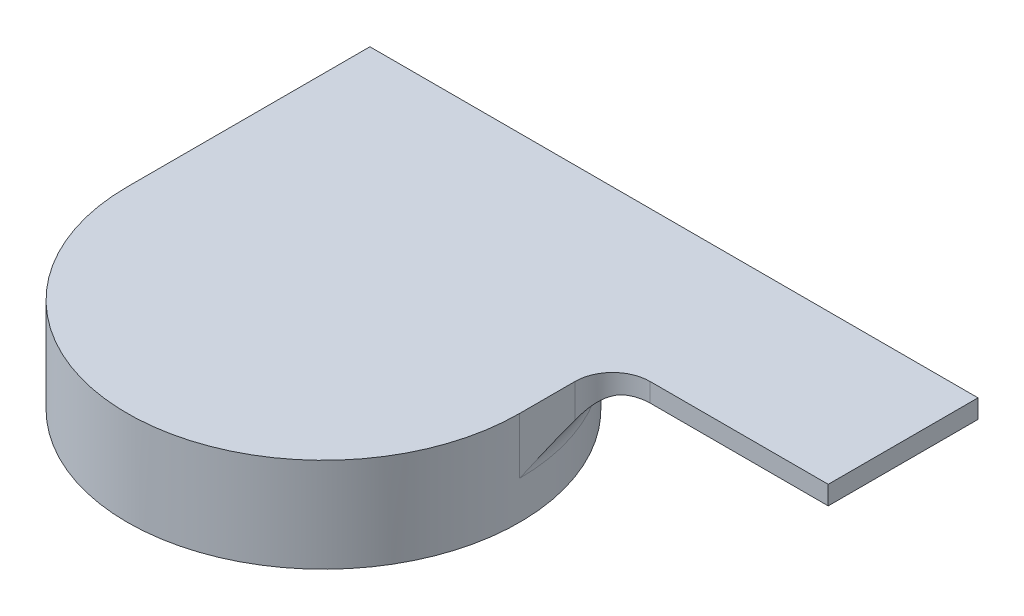
SolidWorks part; units mm, degrees
ref_plane "Front Plane" through (0, 0, 0) normal (0, 0, 1) x (1, 0, 0)
ref_plane "Top Plane" through (0, 0, 0) normal (0, 1, 0) x (1, 0, 0)
ref_plane "Right Plane" through (0, 0, 0) normal (1, 0, 0) x (0, 0, -1)
sketch "Sketch1" plane through (0, 0, 0) normal (0, 1, 0) x (1, 0, 0)
  line L0 (-1.1049, 0) -> (-33.274, 0) construction
  line L1 (-1.1049, 0) -> (33.274, 0) construction
  circle A0 centre (0, 0) radius 33.274
extrude "Boss-Extrude1" add sketch "Sketch1" along normal blind 16.002
sketch "Sketch2" plane through (0, 16.002, 0) normal (0, 1, 0) x (1, 0, 0)
  line L0 (0, 0) -> (-33.274, 0) construction
  line L1 (0, 0) -> (33.274, 0) construction
  line L2 (-33.274, 0) -> (-33.274, 41.148)
  line L3 (-33.274, 41.148) -> (69.85, 41.148)
  line L4 (69.85, 41.148) -> (69.85, 15.748)
  line L5 (33.274, 0) -> (33.274, 15.748)
  line L6 (33.274, 15.748) -> (69.85, 15.748)
  circle A0 centre (0, 0) radius 33.274 construction
  circle A2 centre (0, 0) radius 33.274
  arc A3 (-33.274, 0) -> (33.274, 0) centre (0, 0) ccw
  dimension "D1" = 0
extrude "Boss-Extrude2" add sketch "Sketch2" against normal blind 3.175
fillet "Fillet1" radius 6.35 1 edges at (0, 12.827, -33.274)
fillet "Fillet2" radius 6.35 1 edges at (33.274, 14.0863, -15.748)
